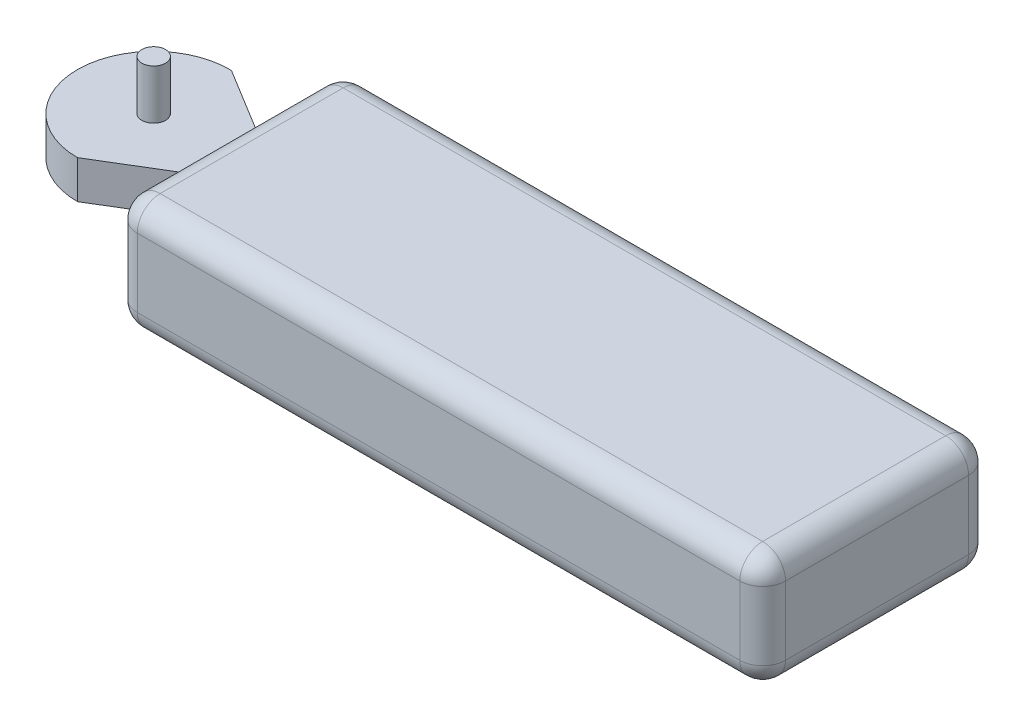
SolidWorks part; units mm, degrees
ref_plane "Front Plane" through (0, 0, 0) normal (0, 0, 1) x (1, 0, 0)
ref_plane "Top Plane" through (0, 0, 0) normal (0, 1, 0) x (1, 0, 0)
ref_plane "Right Plane" through (0, 0, 0) normal (1, 0, 0) x (0, 0, -1)
sketch "Sketch1" plane through (8.0354, 0, 0) normal (0, 1, 0) x (1, 0, 0)
  line L1 (-23.7262, 13.9924) -> (-3.7262, 13.9924)
  line L2 (-23.7262, 13.9924) -> (-23.7262, -8.0076)
  line L3 (-23.7262, -8.0076) -> (-3.7262, -8.0076)
  line L4 (-3.7262, 13.9924) -> (-3.7262, -8.0076)
  dimension "D1" = 20
  dimension "D2" = 22
extrude "Boss-Extrude1" add sketch "Sketch1" along normal blind 5
sketch "Sketch2" plane through (8.0354, 5, 0) normal (0, 1, 0) x (1, 0, 0)
  line L0 (-23.7262, 13.9924) -> (-23.7262, -8.0076) construction
  line L1 (-3.7262, 13.9924) -> (-23.7262, 13.9924) construction
  circle A0 centre (-13.7262, 2.9924) radius 1.55
  dimension "D1" = 3.1
  dimension "D3" = 11
  dimension "D2" = 10
extrude "Boss-Extrude2" add sketch "Sketch2" along normal blind 6.5 and the other way blind 11.5
sketch "Sketch7" plane through (8.0354, 11.5, 0) normal (0, 1, 0) x (1, 0, 0)
  line L0 (-23.7262, 13.9924) -> (-4.0438, 13.9924)
  line L1 (-23.7262, 13.9924) -> (-23.7262, -8.0076)
  line L3 (-23.7262, -8.0076) -> (-3.7262, -8.0076) construction
  line L5 (-3.7262, 13.9924) -> (-23.7262, 13.9924) construction
  line L6 (-23.7262, -8.0076) -> (-3.8204, -8.0076)
  line L7 (-13.7262, -7.0076) -> (-3.8204, -1.0076)
  line L8 (-13.5357, 12.9906) -> (-3.7262, 6.9924)
  line L9 (-3.7262, -8.0076) -> (-3.7262, 13.9924) construction
  line L10 (-3.7262, 6.9924) -> (-3.8204, -1.0076)
  line L11 (-3.8204, -1.0076) -> (-3.8204, -8.0076)
  line L12 (-23.7262, -8.0076) -> (-23.7262, 13.9924)
  line L13 (-3.7262, 13.9924) -> (-3.8204, -8.0076)
  line L14 (-13.5357, 12.9906) -> (-13.5357, 13.9924)
  line L15 (-13.5357, 13.9924) -> (-3.7262, 13.9924)
  line L16 (-3.7262, 6.9924) -> (-13.5357, 12.9906)
  arc A0 (-13.5357, 12.9906) -> (-13.7262, -7.0076) centre (-13.7262, 2.9924) ccw
  dimension "D3" = 10
  dimension "D1" = 7
  dimension "D2" = 7
sketch "Sketch8" plane through (4.3092, 0, 0) normal (1, 0, 0) x (0, 0, -1)
  line L0 (-8.0076, 0) -> (13.9924, 0) construction
  line L1 (-12.163, 8.5) -> (17.837, 8.5)
  line L2 (-12.163, 8.5) -> (-12.163, -6.5)
  line L3 (-12.163, -6.5) -> (17.837, -6.5)
  line L4 (17.837, 8.5) -> (17.837, -6.5)
  dimension "D1" = 30
  dimension "D2" = 15
  dimension "D3" = 8.5
extrude "Boss-Extrude3" add sketch "Sketch8" along normal blind 85
fillet "Fillet1" radius 3 1 edges at (46.8092, -6.5, 12.163) type face fillet first side face at (46.8092, 1, 12.163) second side face at (46.8092, -6.5, -2.837)
fillet "Fillet2" radius 3 1 edges at (46.8092, 8.5, 12.163) type face fillet first side face at (46.8092, 2.5, 12.163) second side face at (46.8092, 8.5, -2.837)
fillet "Fillet3" radius 3 1 edges at (46.8092, 8.5, -17.837) type face fillet first side face at (46.8092, 8.5, -4.337) second side face at (46.8092, 1, -17.837)
fillet "Fillet4" radius 3 1 edges at (46.8092, -6.5, -17.837) type face fillet first side face at (46.8092, -6.5, -4.337) second side face at (46.8092, -0.5, -17.837)
fillet "Fillet5" radius 3 1 edges at (89.3092, -6.5, -2.837) type face fillet first side face at (89.3092, 1, -2.837) second side face at (46.8092, -6.5, -2.837)
fillet "Fillet6" radius 3 1 edges at (4.3092, 1, 12.163) type face fillet first side face at (4.3092, 1, -2.837) second side face at (45.3092, 1, 12.163)
extrude "Cut-Extrude1" cut sketch "Sketch7" against normal blind 20 contours A0 L12 L6 L11 L7 region at (-12.9227, 11.5, 4.2395)
extrude "Cut-Extrude2" cut sketch "Sketch7<4>" against normal blind 20 contours L15 L0 L14 L8 L13 | A0 L14 L0 L1 region at (-12.5358, 11.5, -11.6389) region at (0.6202, 11.5, -11.6234)
sketch "Sketch7<4>" plane through (8.0354, 11.5, 0) normal (0, 1, 0) x (1, 0, 0) same geometry as "Sketch7"
